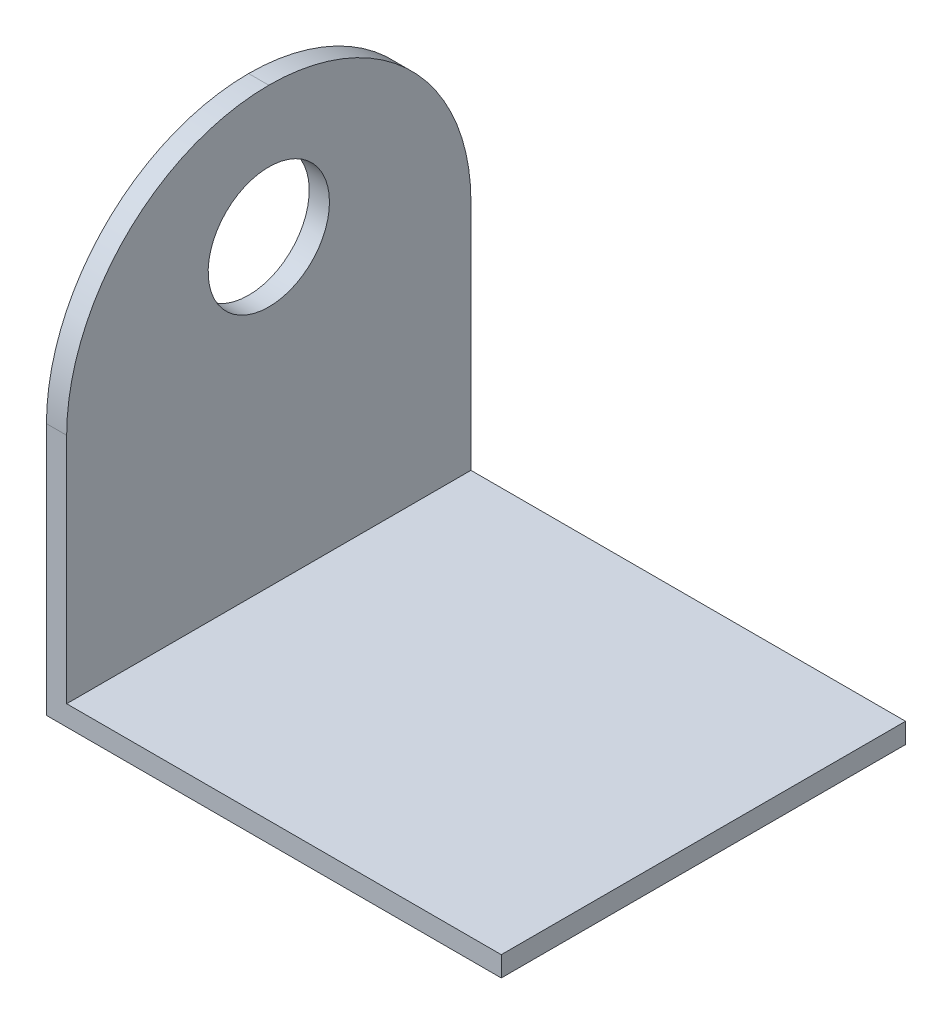
SolidWorks part; units mm, degrees
ref_plane "Front Plane" through (0, 0, 0) normal (0, 0, 1) x (1, 0, 0)
ref_plane "Top Plane" through (0, 0, 0) normal (0, 1, 0) x (1, 0, 0)
ref_plane "Right Plane" through (0, 0, 0) normal (1, 0, 0) x (0, 0, -1)
sketch "Sketch1" plane through (0, 0, 0) normal (0, 0, 1) x (1, 0, 0)
  line L0 (0, 0) -> (0, -45)
  line L1 (0, -45) -> (45, -45)
  line L2 (2, 0) -> (2, -43)
  line L3 (2, -43) -> (45, -43)
  line L4 (0, 0) -> (2, 0)
  line L5 (45, -43) -> (45, -45)
  dimension "D1" = 45
  dimension "D2" = 45
  dimension "D3" = 2
extrude "Boss-Extrude1" add sketch "Sketch1" against normal blind 40
fillet "Fillet1" radius 20 1 edges at (1, 0, -40)
fillet "Fillet2" radius 20 1 edges at (1, 0, 0)
sketch "Sketch2" plane through (0, 0, 0) normal (-1, 0, 0) x (0, 0, 1)
  line L2 (-40, -20) -> (-40, -45) construction
  circle A0 centre (-20, -13.0022) radius 6
  point P3 (0, 0)
  dimension "D1" = 12
  dimension "D3" = 13.0022
  dimension "D2" = 20
extrude "Cut-Extrude1" cut sketch "Sketch2" against normal blind 10
